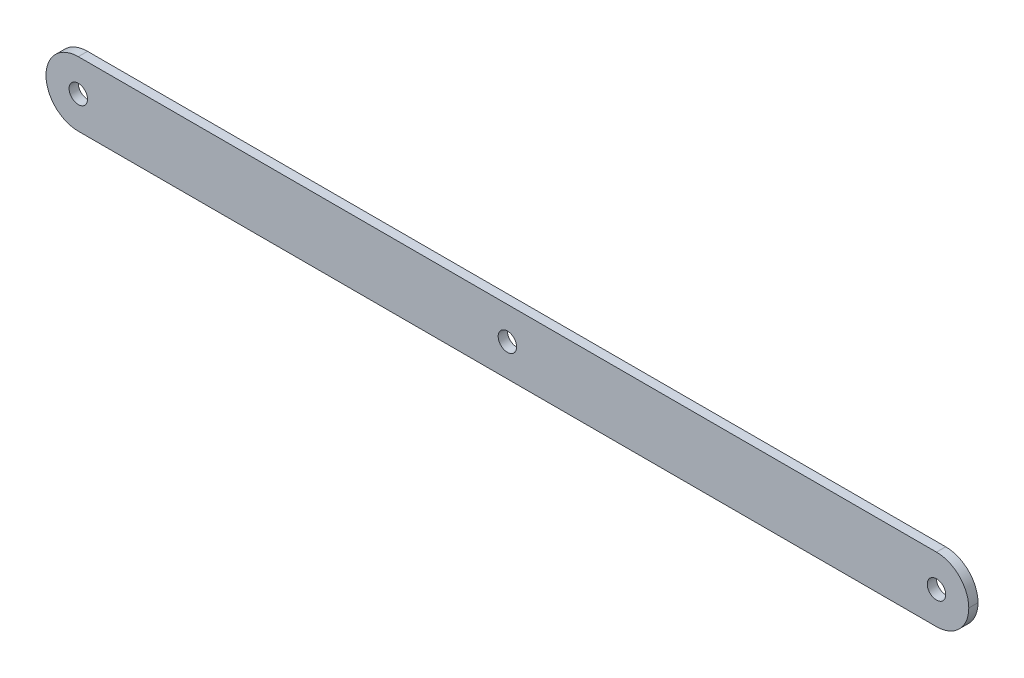
SolidWorks part; units mm, degrees
ref_plane "Front Plane" through (0, 0, 0) normal (0, 0, 1) x (1, 0, 0)
ref_plane "Top Plane" through (0, 0, 0) normal (0, 1, 0) x (1, 0, 0)
ref_plane "Right Plane" through (0, 0, 0) normal (1, 0, 0) x (0, 0, -1)
sketch "Sketch1" plane through (0, 0, 0) normal (0, 0, 1) x (1, 0, 0)
  line L1 (-250, 17.5) -> (250, 17.5)
  line L2 (-250, 17.5) -> (-250, -17.5)
  line L3 (-250, -17.5) -> (250, -17.5)
  line L4 (250, 17.5) -> (250, -17.5)
  line L5 (-250, 17.5) -> (250, -17.5) construction
  line L6 (-250, -17.5) -> (250, 17.5) construction
  point P0 (0, 0)
  dimension "D1" = 35
  dimension "D2" = 500
extrude "Boss-Extrude1" add sketch "Sketch1" along normal mid plane 5
fillet "Fillet1" radius 17.5 4 edges at (-250, -17.5, 0) (-250, 17.5, 0) (250, -17.5, 0) (250, 17.5, 0)
sketch "Sketch2" plane through (0, 0, 2.5) normal (0, 0, 1) x (1, 0, 0)
  line L0 (0, 17.5) -> (0, -17.5) construction
  line L1 (232.5, 17.5) -> (-232.5, 17.5) construction
  line L2 (-232.5, -17.5) -> (232.5, -17.5) construction
  circle A0 centre (0, 0) radius 5
  circle A1 centre (232.5, 0) radius 5
  circle A2 centre (-232.5, 0) radius 5
  dimension "D1" = 10
  dimension "D2" = 10
extrude "Cut-Extrude1" cut sketch "Sketch2" against normal blind 5
